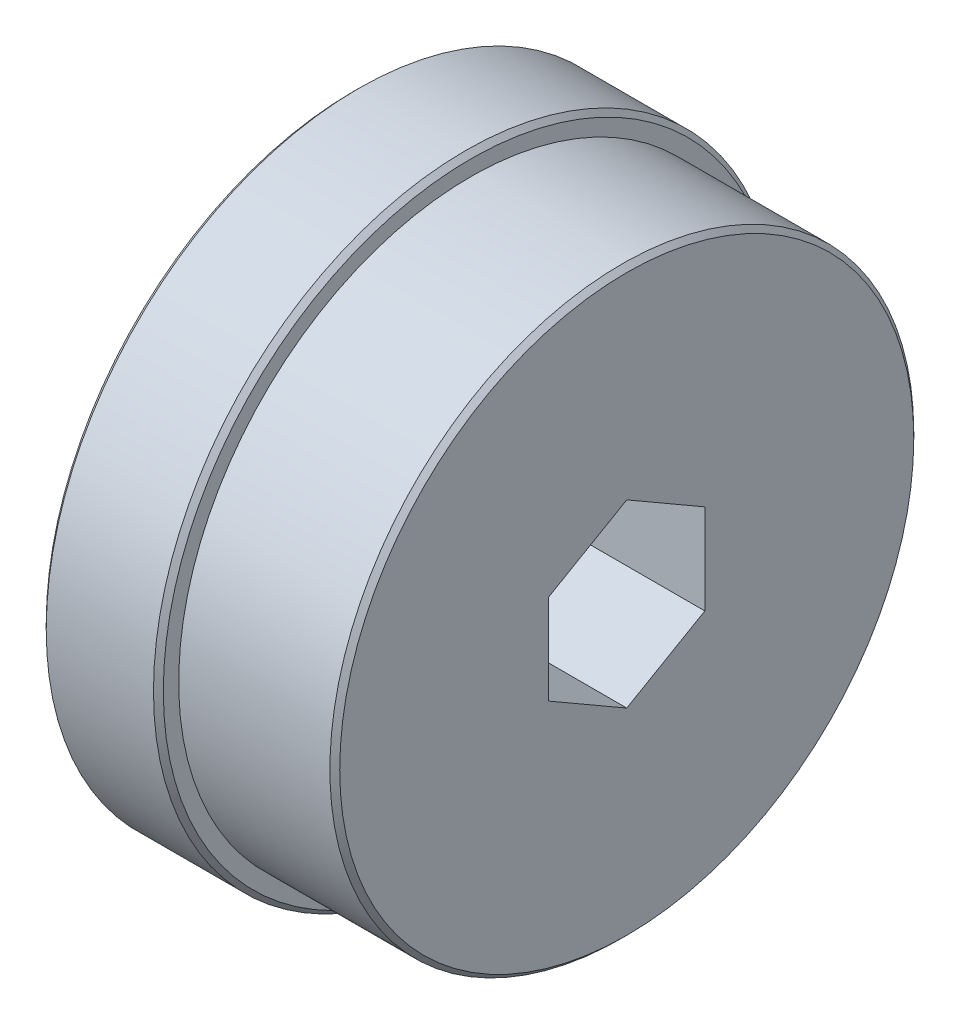
SolidWorks part; units mm, degrees
material "Nylon 101"
ref_plane "Front Plane" through (0, 0, 0) normal (0, 0, 1) x (1, 0, 0)
ref_plane "Top Plane" through (0, 0, 0) normal (0, 1, 0) x (1, 0, 0)
ref_plane "Right Plane" through (0, 0, 0) normal (1, 0, 0) x (0, 0, -1)
sketch "Sketch1" plane through (0, 0, 0) normal (1, 0, 0) x (0, 0, -1)
  circle A0 centre (0, 0) radius 23.749
  dimension "D1" = 47.498
extrude "Boss-Extrude1" add sketch "Sketch1" along normal blind 12.7
sketch "Sketch2" plane through (0, 0, 0) normal (-1, 0, 0) x (0, 0, 1)
  circle A0 centre (0, 0) radius 25.4
  dimension "D1" = 50.8
extrude "Boss-Extrude2" add sketch "Sketch2" along normal blind 9.525
sketch "Sketch3" plane through (-9.525, 0, 0) normal (-1, 0, 0) x (0, 0, 1)
  circle A0 centre (0, 0) radius 14.2875
  dimension "D1" = 28.575
chamfer "Chamfer1" distance 0.4 angle 45 3 edges at (12.7, 0, -23.749) (-9.525, 0, 25.4) (0, 0, 25.4)
sketch "Sketch4" plane through (-9.525, 0, 0) normal (-1, 0, 0) x (0, 0, 1)
  line L1 (0, 7.3323) -> (-6.35, 3.6662)
  line L2 (-6.35, 3.6662) -> (-6.35, -3.6662)
  line L3 (-6.35, -3.6662) -> (0, -7.3323)
  line L4 (0, -7.3323) -> (6.35, -3.6662)
  line L5 (6.35, -3.6662) -> (6.35, 3.6662)
  line L6 (6.35, 3.6662) -> (0, 7.3323)
  circle A0 centre (0, 0) radius 6.35 construction
  dimension "D1" = 12.7
extrude "Cut-Extrude1" cut sketch "Sketch4" against normal through all
